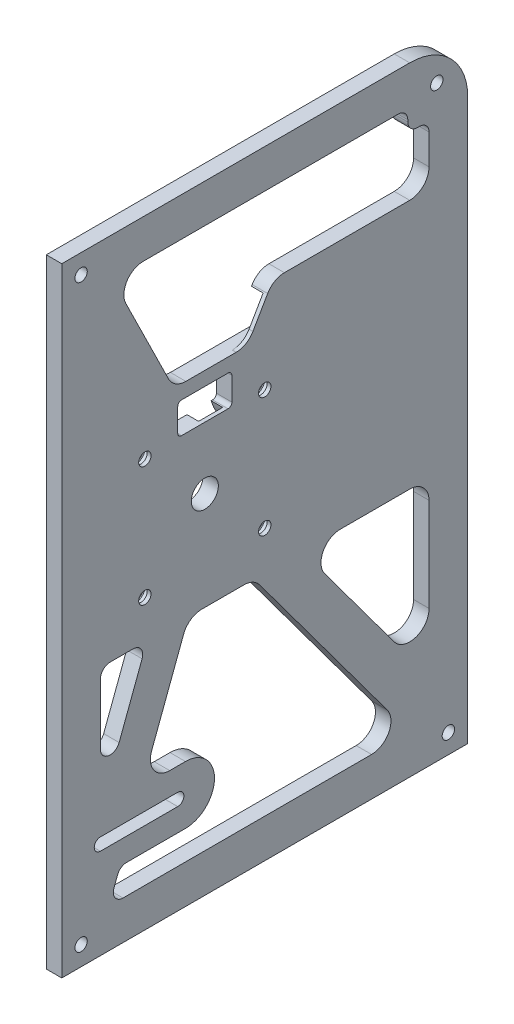
SolidWorks part; units mm, degrees
ref_plane "Front Plane" through (0, 0, 0) normal (0, 0, 1) x (1, 0, 0)
ref_plane "Top Plane" through (0, 0, 0) normal (0, 1, 0) x (1, 0, 0)
ref_plane "Right Plane" through (0, 0, 0) normal (1, 0, 0) x (0, 0, -1)
sketch "Sketch2" plane through (0, 0, 0) normal (1, 0, 0) x (0, 0, -1)
  line L1 (0, 0) -> (105, 0)
  line L2 (0, 0) -> (0, 160)
  line L3 (0, 160) -> (90, 160)
  line L4 (105, 0) -> (105, 145)
  line L8 (90, 145) -> (105, 160) construction
  line L9 (90, 145) -> (105, 145) construction
  line L17 (10, 25) -> (30, 25) construction
  line L22 (10, 26.6) -> (30, 26.6)
  line L23 (10, 23.4) -> (30, 23.4)
  line L35 (37, 106) -> (37, 90) construction
  line L44 (44, 106) -> (30, 106)
  line L49 (44, 106) -> (44, 114)
  line L50 (44, 114) -> (30, 114)
  line L51 (30, 106) -> (30, 114)
  line L52 (44, 106) -> (30, 114) construction
  line L53 (44, 114) -> (30, 106) construction
  line L103 (90, 160) -> (105, 160) construction
  line L104 (105, 160) -> (105, 145) construction
  arc A0 (90, 160) -> (105, 145) centre (90, 145) cw
  circle A11 centre (97, 152) radius 1.6
  arc A16 (10, 26.6) -> (10, 23.4) centre (10, 25) ccw
  arc A17 (30, 23.4) -> (30, 26.6) centre (30, 25) ccw
  circle A19 centre (52.5, 105.5) radius 1.6
  circle A22 centre (37, 90) radius 3.5
  circle A24 centre (52.5, 74.5) radius 1.6
  circle A25 centre (21.5, 74.5) radius 1.6
  circle A26 centre (21.5, 105.5) radius 1.6
  circle A29 centre (5, 5) radius 1.6
  circle A30 centre (100, 5) radius 1.6
  circle A31 centre (5, 155) radius 1.6
  point P7 (-20.3463, 100.4836)
  point P8 (-20.3463, 110)
  point P9 (-17.2687, 110)
  point P11 (-7.7956, 111.9756)
  point P12 (-15.1653, 108.0888)
  point P23 (34.5808, 88.2259)
  point P27 (-14.3663, 119.9153)
  point P28 (-17.6894, 102.0261)
  point P34 (20, 25)
  point P43 (-8.2747, 124.022)
  point P47 (-13.2022, 102.0261)
  point P52 (37, 110)
  point P53 (46.5, 99)
  point P58 (46.5, 115)
  point P59 (25.5, 115)
  point P60 (25.5, 99)
  point P64 (95.0808, 5.7259)
  point P66 (-17.6894, 103.6386)
  point P67 (37, 90)
  point P69 (34.1752, 91.0101)
  point P72 (4.6752, 8.5101)
  point P73 (39.8248, 88.9899)
  point P74 (10.3248, 6.4899)
  point P75 (-17.2687, 105.5)
  point P76 (7.2565, 156.0762)
  point P77 (-15.1653, 100.4836)
  point P78 (2.7435, 153.9238)
  point P85 (-12.3658, 115.0209)
  dimension "D1" = 15
  dimension "D6" = 3.2
  dimension "D7" = 5
  dimension "D9" = 5
  dimension "D10" = 5
  dimension "D11" = 8
  dimension "D14" = 3.2
  dimension "D15" = 20
  dimension "D20" = 37
  dimension "D21" = 3.2
  dimension "D22" = 70
  dimension "D23" = 15.5
  dimension "D34" = 7
  dimension "D2" = 160
  dimension "D3" = 105
  dimension "D5" = 45
  dimension "D18" = 25
  dimension "D24" = 15.5
  dimension "D25" = 20
  dimension "D28" = 4
  dimension "D29" = 31
  dimension "D31" = 8
  dimension "D30" = 14
  dimension "D33" = 31
  dimension "D40" = 5
  dimension "D41" = 5
  dimension "D42" = 5
  dimension "D49" = 10
extrude "Boss-Extrude1" add sketch "Sketch2" along normal blind 4
chamfer "Chamfer1" distance 1.5 angle 45 8 edges at (0, 105.5, -54.1) (0, 155, -6.6) (0, 152, -98.6) (0, 74.5, -54.1) (0, 74.5, -23.1) (0, 105.5, -23.1) (0, 5, -101.6) (0, 5, -6.6)
fillet "Fillet2" radius 1 4 edges at (2, 114, -44) (2, 106, -44) (2, 106, -30) (2, 114, -30)
sketch "Sketch3" plane through (0, 0, 0) normal (-1, 0, 0) x (0, 0, 1)
  line L0 (-105, 95.5) -> (-52.5, 95.5) construction
  line L1 (-105, 0) -> (-105, 145) construction
  line L4 (-39.5, 106) -> (-38.9808, 107.9314) construction
  line L5 (-52.5, 95.5) -> (-42.3226, 95.5) construction
  line L6 (-37, 106) -> (-37, 90) construction
  line L7 (-44, 106) -> (-30, 106) construction
  line L8 (-105, 92.5) -> (-52.5, 92.5)
  line L9 (-36.6029, 105.2212) -> (-36.0837, 107.1526)
  line L10 (-105, 98.5) -> (-52.5, 98.5)
  line L11 (-42.3971, 106.7788) -> (-41.8779, 108.7102)
  line L12 (-52.5, 105.5) -> (-52.5, 74.5) construction
  line L13 (-105, 92.5) -> (-105, 98.5)
  line L14 (-36.0837, 107.1526) -> (-41.8779, 108.7102)
  line L15 (-97, 152) -> (-37, 90) construction
  line L17 (-42.3226, 95.5) -> (-39.5, 106) construction
  spline S0 degree 2 poles (-52.5, 95.5) (-42.3226, 95.5) (-39.5, 106) knots 0 0 0 1 1 1 construction
  spline S1 degree 1 poles (-52.5, 92.5) (-36.6029, 105.2212) knots 0 0 1 1 construction
  spline S2 degree 3 poles (-52.5, 92.5) (-52.0179, 92.5) (-51.0448, 92.5315) (-49.1758, 92.7252) (-46.9363, 93.2222) (-44.4522, 94.2535) (-42.2241, 95.7235) (-40.3092, 97.5997) (-38.7341, 99.8266) (-37.6975, 101.9403) (-37.0242, 103.7646) (-36.7331, 104.7367) (-36.6029, 105.2212) knots 0 0 0 0 0.0625 0.125 0.25 0.375 0.5 0.625 0.75 0.875 0.9375 1 1 1 1
  spline S3 degree 1 poles (-52.5, 98.5) (-42.3971, 106.7788) knots 0 0 1 1 construction
  spline S4 degree 3 poles (-52.5, 98.5) (-52.1527, 98.5) (-51.4407, 98.5232) (-50.1604, 98.6576) (-48.7274, 98.9809) (-47.274, 99.5903) (-46.0218, 100.417) (-44.9165, 101.4946) (-43.9317, 102.8748) (-43.2157, 104.3229) (-42.7222, 105.6559) (-42.4966, 106.4087) (-42.3971, 106.7788) knots 0 0 0 0 0.0625 0.125 0.25 0.375 0.5 0.625 0.75 0.875 0.9375 1 1 1 1
  dimension "D4" = 2
  dimension "D1" = 3
  dimension "D3" = 10
  dimension "D6" = 2.5
  dimension "D2" = 3
extrude "Cut-Extrude1" cut sketch "Sketch3" against normal blind 3
sketch "Sketch6" plane through (0, 0, 0) normal (-1, 0, 0) x (0, 0, 1)
  line L0 (-105, 122) -> (-75, 122) construction
  line L2 (-105, 0) -> (-105, 145) construction
  line L3 (-75, 122) -> (-63, 122) construction
  line L4 (-63, 122) -> (-35, 122) construction
  line L5 (-63, 117.6) -> (-35, 117.6)
  line L6 (-63, 126.4) -> (-35, 126.4)
  line L7 (-105, 119.8) -> (-75, 119.8)
  line L9 (-105, 124.2) -> (-75, 124.2)
  line L10 (-75, 124.2) -> (-63, 126.4)
  line L11 (-75, 119.8) -> (-63, 117.6)
  line L12 (-35, 117.6) -> (-35, 126.4)
  line L14 (-39, 122) -> (-39, 121.596) construction
  line L15 (-37, 122) -> (-37, 120.6455) construction
  line L16 (-37, 106) -> (-37, 90) construction
  dimension "D5" = 12
  dimension "D6" = 28
  dimension "D7" = 32
  dimension "D8" = 4
  dimension "D9" = 2
  dimension "D1" = 4.4
  dimension "D2" = 4.4
  dimension "D3" = 2.2
  dimension "D4" = 2.2
extrude "Cut-Extrude3" cut sketch "Sketch6" against normal blind 3 and the other way through all flip side to cut
sketch "Sketch7" plane through (0, 0, 0) normal (-1, 0, 0) x (0, 0, 1)
  line L0 (-10, 64.5) -> (-10, 32.4725)
  line L2 (-10, 64.5) -> (-22.0574, 64.5)
  line L5 (-32, 17.5) -> (-15.0485, 17.5)
  line L7 (-100, 5) -> (-37, 90) construction
  line L8 (-37, 90) -> (-5, 155) construction
  line L9 (-37, 90) -> (-5, 5) construction
  line L10 (-37, 90) -> (-97, 152) construction
  line L11 (0, 0) -> (0, 160) construction
  line L12 (-10, 25) -> (-30, 25) construction
  line L13 (-89.5, 150) -> (-13.0346, 150)
  line L15 (-95, 144.5) -> (-95, 129.2)
  line L16 (-95, 129.2) -> (-54.6973, 129.2)
  line L18 (0, 160) -> (-90, 160) construction
  line L20 (-95, 64.5) -> (-95, 20.143)
  line L23 (-90.0705, 10) -> (-12.2249, 10)
  line L27 (-95, 144.5) -> (-89.5, 144.5)
  line L28 (-89.5, 144.5) -> (-89.5, 150)
  line L31 (-105, 0) -> (-105, 145) construction
  line L32 (-105, 124.2) -> (-75, 124.2) construction
  line L33 (-35, 117.6) -> (-63, 117.6) construction
  line L34 (-54.6973, 129.2) -> (-48, 117.6)
  line L35 (-35, 117.6) -> (-63, 117.6) construction
  line L36 (-62.1236, 64.5) -> (-95, 20.143)
  line L37 (-49.6764, 64.5) -> (-90.0705, 10)
  line L38 (-32.7426, 64.5) -> (-20.6955, 32.5)
  line L39 (-22.0574, 64.5) -> (-10, 32.4725)
  line L40 (-62.1236, 64.5) -> (-95, 64.5)
  line L41 (-32.7426, 64.5) -> (-49.6764, 64.5)
  line L42 (-20.6955, 32.5) -> (-32, 32.5)
  line L43 (-12.2249, 10) -> (-15.0485, 17.5)
  line L44 (-13.0346, 150) -> (-28.9854, 117.6)
  line L46 (-28.9854, 117.6) -> (-48, 117.6)
  line L47 (0, 0) -> (-105, 0) construction
  arc A0 (-32, 32.5) -> (-32, 17.5) centre (-32, 25) ccw
  point P5 (-32, 32.5)
  point P9 (-32, 17.5)
  dimension "D3" = 2
  dimension "D2" = 7.5
  dimension "D4" = 10
  dimension "D5" = 5
  dimension "D6" = 120
  dimension "D7" = 5
  dimension "D8" = 5
  dimension "D9" = 10
  dimension "D10" = 10
  dimension "D11" = 7.5
  dimension "D12" = 7.5
  dimension "D13" = 5
  dimension "D14" = 7.5
  dimension "D15" = 15
  dimension "D16" = 5
  dimension "D17" = 5
  dimension "D18" = 5
  dimension "D19" = 10
  dimension "D20" = 10
  dimension "D21" = 10
extrude "Cut-Extrude4" cut sketch "Sketch7" against normal through all
fillet "Fillet5" radius 5 12 edges at (2, 32.5, -20.6955) (2, 129.2, -95) (2, 150, -13.0346) (2, 117.6, -28.9854) (2, 129.2, -54.6973) (3.5, 117.6, -48) (2, 64.5, -49.6764) (2, 10, -90.0705) (2, 20.143, -95) (2, 64.5, -95) (2, 64.5, -62.1236) (2, 64.5, -32.7426)
fillet "Fillet6" radius 2.5 8 edges at (2, 64.5, -10) (2, 64.5, -22.0574) (2, 10, -12.2249) (2, 17.5, -15.0485) (2, 32.4725, -10) (2, 150, -89.5) (2, 144.5, -89.5) (2, 144.5, -95)
sketch "Sketch4" plane through (0, 0, 0) normal (-1, 0, 0) x (0, 0, 1)
  line L0 (-105, 124.2) -> (-75, 124.2) construction
  line L1 (-83, 98.5) -> (-75.5, 98.5)
  line L2 (-83, 98.5) -> (-83, 95.5)
  line L3 (-83, 95.5) -> (-75.5, 95.5)
  line L4 (-75.5, 98.5) -> (-75.5, 95.5)
  line L5 (-77.5, 124.2) -> (-85, 124.2)
  line L6 (-105, 92.5) -> (-97.5, 92.5)
  line L7 (-105, 92.5) -> (-105, 95.5)
  line L8 (-105, 95.5) -> (-97.5, 95.5)
  line L9 (-97.5, 92.5) -> (-97.5, 95.5)
  line L10 (-53.5, 92.5) -> (-61, 92.5)
  line L11 (-53.5, 92.5) -> (-53.5, 95.5)
  line L12 (-53.5, 95.5) -> (-61, 95.5)
  line L13 (-61, 92.5) -> (-61, 95.5)
  line L14 (-52.5, 98.5) -> (-105, 98.5) construction
  line L15 (-77.5, 124.2) -> (-77.5, 122)
  line L16 (-77.5, 122) -> (-85, 122)
  line L17 (-105, 92.5) -> (-52.5, 92.5) construction
  line L18 (-85, 124.2) -> (-85, 122)
  line L20 (-105, 119.8) -> (-97.5, 119.8)
  line L21 (-105, 119.8) -> (-105, 122)
  line L22 (-105, 122) -> (-97.5, 122)
  line L23 (-97.5, 119.8) -> (-97.5, 122)
  dimension "D1" = 7.5
  dimension "D2" = 7.5
  dimension "D3" = 7.5
  dimension "D4" = 3
  dimension "D5" = 3
  dimension "D6" = 3
  dimension "D7" = 14.5
  dimension "D8" = 14.5
  dimension "D9" = 7.5
  dimension "D10" = 2.2
  dimension "D11" = 2.2
  dimension "D12" = 7.5
  dimension "D13" = 12.5
extrude "Boss-Extrude2" add sketch "Sketch4" against normal blind 1
chamfer "Chamfer2" distance 1.5 angle 45 5 edges at (1, 124.2, -81.25) (1, 119.8, -101.25) (1, 92.5, -57.25) (1, 92.5, -101.25) (1, 98.5, -79.25)
fillet "Fillet7" radius 1.5 8 edges at (0.5, 122, -85) (0.5, 122, -97.5) (0.5, 122, -77.5) (0.5, 95.5, -53.5) (0.5, 95.5, -61) (0.5, 95.5, -75.5) (0.5, 95.5, -83) (0.5, 95.5, -97.5)
sketch "Sketch8" plane through (0, 0, 0) normal (-1, 0, 0) x (0, 0, 1)
  circle A0 centre (-52.5, 105.5) radius 3.25
  circle A1 centre (-21.5, 105.5) radius 3.25
  circle A2 centre (-21.5, 74.5) radius 3.25
  circle A3 centre (-52.5, 74.5) radius 3.25
  dimension "D1" = 6.5
extrude "Cut-Extrude5" cut sketch "Sketch8" against normal blind 3
chamfer "Chamfer3" distance 1 angle 45 4 edges at (0, 74.5, -18.25) (0, 74.5, -49.25) (0, 105.5, -18.25) (0, 105.5, -49.25)
